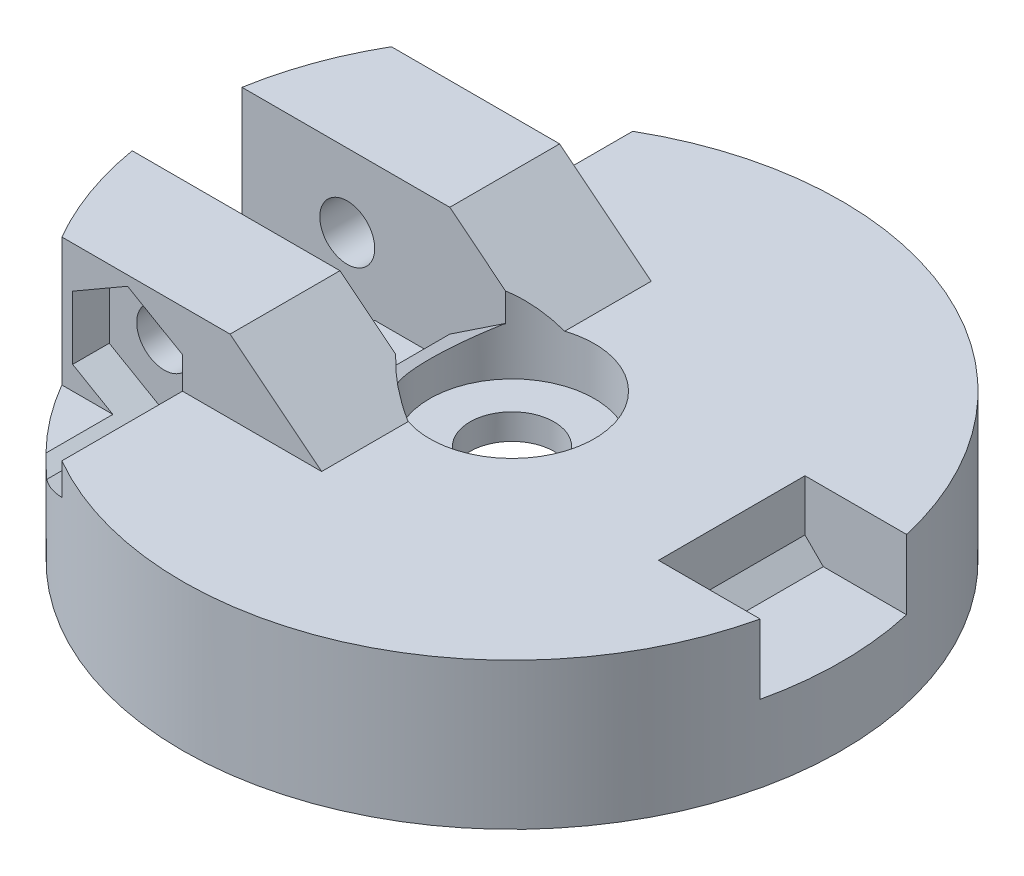
SolidWorks part; units mm, degrees
ref_plane "Front Plane" through (0, 0, 0) normal (0, 0, 1) x (1, 0, 0)
ref_plane "Top Plane" through (0, 0, 0) normal (0, 1, 0) x (1, 0, 0)
ref_plane "Right Plane" through (0, 0, 0) normal (1, 0, 0) x (0, 0, -1)
sketch "Sketch1" plane through (0, 0, 0) normal (0, 1, 0) x (1, 0, 0)
  circle A0 centre (0, 0) radius 9
  dimension "D1" = 18
extrude "Boss-Extrude1" add sketch "Sketch1" along normal blind 6
sketch "Sketch2" plane through (0, 6, 0) normal (0, 1, 0) x (1, 0, 0)
  circle A0 centre (0, 0) radius 1.15
  dimension "D1" = 2.3
extrude "Cut-Extrude1" cut sketch "Sketch2" against normal through all
sketch "Sketch5" plane through (0, 6, 0) normal (0, 1, 0) x (1, 0, 0)
  line L1 (-3.2, 4.5) -> (-7.7942, 4.5)
  line L2 (-3.2, 4.5) -> (-3.2, 8.4119)
  line L3 (-3.2, 8.4119) -> (-7.7942, 8.4119)
  line L4 (-7.7942, 4.5) -> (-7.7942, 8.4119)
  circle A2 centre (0, 0) radius 9 construction
  dimension "D1" = 3.2
  dimension "D2" = 4.5
extrude "Cut-Extrude3" cut sketch "Sketch5" against normal blind 3.5
mirror "Mirror1" about plane through (0, 0, 0) normal (0, 0, 1) of "Cut-Extrude3"
sketch "Sketch6" plane through (0, 6, 0) normal (0, 1, 0) x (1, 0, 0)
  line L0 (-3.2, -4.5) -> (-3.2, -8.4119) construction
  line L1 (-3.2, 9) -> (23.0525, 9)
  line L2 (-3.2, 9) -> (-3.2, -20.0526)
  line L3 (-3.2, -20.0526) -> (23.0525, -20.0526)
  line L4 (23.0525, 9) -> (23.0525, -20.0526)
  arc A0 (-3.2, -8.4119) -> (-3.2, 8.4119) centre (0, 0) ccw construction
extrude "Cut-Extrude4" cut sketch "Sketch6" against normal blind 2
sketch "Sketch7" plane through (0, 6, 0) normal (0, 1, 0) x (1, 0, 0)
  line L0 (-3.2, 4.5) -> (-3.2, -4.5) construction
  line L1 (-3.2, -1.5) -> (-12.173, -1.5)
  line L2 (-3.2, -1.5) -> (-3.2, 1.5)
  line L3 (-3.2, 1.5) -> (-12.173, 1.5)
  line L4 (-12.173, -1.5) -> (-12.173, 1.5)
  dimension "D1" = 1.5
  dimension "D2" = 3
extrude "Cut-Extrude5" cut sketch "Sketch7" against normal blind 3.7
sketch "Sketch11" plane through (0, 0, 0) normal (0, -1, 0) x (1, 0, 0)
  circle A0 centre (0, 0) radius 5.5
  dimension "D1" = 11
extrude "Cut-Extrude7" cut sketch "Sketch11" against normal blind 2
sketch "Sketch12" plane through (0, 4, 0) normal (0, 1, 0) x (1, 0, 0)
  line L1 (6, -2) -> (11.6408, -2)
  line L2 (6, -2) -> (6, 2)
  line L3 (6, 2) -> (11.6408, 2)
  line L4 (11.6408, -2) -> (11.6408, 2)
  arc A0 (-3.2, -8.4119) -> (-3.2, 8.4119) centre (0, 0) ccw construction
  dimension "D1" = 6
  dimension "D2" = 2
  dimension "D3" = 2
extrude "Cut-Extrude8" cut sketch "Sketch12" against normal blind 1.9
hole_wizard "CBORE for M1.4 Hex Socket Head Cap Screw1" positions "Sketch8" profile "Sketch9" counterbore size "M1.4" standard "DIN"
sketch "Sketch8" plane through (0, 0, -4.5) normal (0, 0, -1) x (-1, 0, 0)
  line L0 (7.7942, 6) -> (3.2, 6) construction
  point P0 (6, 4)
  dimension "D1" = 2
  dimension "D2" = 6
sketch "Sketch9" plane through (-6, 4, -4.5) normal (1, 0, 0) x (0, 1, 0)
  line L0 (0, 0) -> (0, 10.4506)
  line L1 (0, 10.4506) -> (0.75, 10)
  line L2 (0.75, 10) -> (0.75, 1)
  line L3 (0.75, 1) -> (1.35, 1)
  line L4 (1.35, 1) -> (1.35, 0)
  line L5 (1.35, 0) -> (0, 0)
  line L10 (0, 10.4506) -> (-0.75, 10) construction
  line L11 (0, -6.35) -> (0, 107.95) construction
  dimension "Hole Dia." = 1.5
  dimension "Hole Depth" = 10
  dimension "C'Bore Dia." = 2.7
  dimension "C'Bore Depth" = 1
  dimension "Drill Angle" = 118
fillet "Fillet7" radius 0.5 1 edges at (0, 2, -5.5) type face fillet first side face at (0, 2, -5.5) second side face at (0, 2, -5.5)
sketch "Sketch16" plane through (0, 0, 2) normal (0, 0, -1) x (-1, 0, 0)
  line L0 (-6, 2.1) -> (-6.5, 2.1)
  line L1 (-6, 2.1) -> (-8.775, 2.1) construction
  line L2 (-6.5, 2.1) -> (-6, 2.6)
  line L3 (-6, 2.1) -> (-6, 4) construction
  line L4 (-6, 2.6) -> (-6, 2.1)
  dimension "D1" = 0.5
  dimension "D2" = 0.5
extrude "Boss-Extrude4" add sketch "Sketch16" along normal up to surface (4 mm away) up to face at (7.3875, 3.05, -2)
sketch "Sketch17" plane through (0, 0, 4.5) normal (0, 0, 1) x (1, 0, 0)
  line L0 (-7.7942, 2.5) -> (-7.7942, 6) construction
  line L1 (-4.5, 4.866) -> (-6, 5.7321)
  line L2 (-6, 5.7321) -> (-7.5, 4.866)
  line L3 (-7.5, 4.866) -> (-7.5, 3.134)
  line L4 (-7.5, 3.134) -> (-6, 2.2679)
  line L5 (-6, 2.2679) -> (-4.5, 3.134)
  line L6 (-4.5, 3.134) -> (-4.5, 4.866)
  circle A1 centre (-6, 4) radius 1.5 construction
  dimension "D1" = 1.5
extrude "Cut-Extrude9" cut sketch "Sketch17" against normal blind 1
sketch "Sketch20" plane through (0, 0, 1.5) normal (0, 0, -1) x (-1, 0, 0)
  line L0 (3.2, 4) -> (1.7, 4)
  line L1 (1.7, 4) -> (3.2, 3)
  line L2 (3.2, 2.3) -> (3.2, 4) construction
  line L3 (3.2, 3) -> (3.2, 4)
  dimension "D1" = 1.5
  dimension "D2" = 1
extrude "Cut-Extrude11" cut sketch "Sketch20" along direction (0, 0, 1) on the side of the normal up to surface (3 mm away) up to face at (-6.75, 4, -1.5)
sketch "Sketch21" plane through (0, 0, -4.5) normal (0, 0, -1) x (-1, 0, 0)
  line L0 (3.2, 6) -> (3.2, 4)
  line L1 (3.2, 4) -> (0.7, 4)
  line L2 (0.7, 4) -> (3.2, 6)
  dimension "D1" = 2.5
extrude "Boss-Extrude5" add sketch "Sketch21" along direction (0, 0, 1) on the side against the normal up to surface (3 mm away) up to face at (-6.75, 4, -1.5)
sketch "Sketch22" plane through (0, 0, 4.5) normal (0, 0, 1) x (1, 0, 0)
  line L0 (-3.2, 6) -> (-3.2, 4)
  line L1 (-3.2, 4) -> (-0.7, 4)
  line L2 (-0.7, 4) -> (-3.2, 6)
  dimension "D1" = 2.5
extrude "Boss-Extrude6" add sketch "Sketch22" against normal up to surface (3 mm away) up to face at (-5.25, 4, 1.5)
sketch "Sketch10" plane through (0, 4, 0) normal (0, 1, 0) x (1, 0, 0)
  circle A0 centre (0, 0) radius 2.25
  dimension "D1" = 4.5
extrude "Cut-Extrude6" cut sketch "Sketch10" against normal blind 1.3 and the other way blind 3
sketch "Sketch24" plane through (0, 0, 4.5) normal (0, 0, 1) x (1, 0, 0)
  line L3 (-3.2, 2.5) -> (-3.2, 4)
  line L4 (-3.2, 2.5) -> (-5.5981, 2.5)
  line L5 (-5.5981, 2.5) -> (-4.5, 3.134)
  line L6 (-3.2, 4) -> (-4.5, 4)
  line L7 (-4.5, 3.134) -> (-4.5, 4.866) construction
  line L8 (-4.5, 4) -> (-4.5, 3.134)
extrude "Boss-Extrude8" add sketch "Sketch24" along normal up to surface (3.9119 mm away) up to face at (-2.6435, 3.675, 0)
mirror "Mirror4" about plane through (0, 0, 0) normal (0, 0, 1) of "Boss-Extrude8"
sketch "Sketch25" plane through (0, 0, 4.5) normal (0, 0, 1) x (1, 0, 0)
  line L0 (-5.5981, 2.5) -> (-6.4019, 2.5)
  line L1 (-6.4019, 2.5) -> (-6, 2.2679)
  line L2 (-6, 2.2679) -> (-5.5981, 2.5)
extrude "Cut-Extrude12" cut sketch "Sketch25" along normal blind 3
sketch "Sketch26" plane through (0, 2.3, 0) normal (0, 1, 0) x (1, 0, 0)
  line L1 (-6.95, 1.5) -> (-5.25, 1.5)
  line L2 (-6.95, 1.5) -> (-6.95, -1.5)
  line L3 (-6.95, -1.5) -> (-5.25, -1.5)
  line L4 (-5.25, 1.5) -> (-5.25, -1.5)
  dimension "D1" = 1.7
extrude "Cut-Extrude13" cut sketch "Sketch26" against normal blind 0.3
equation "\"D2@Sketch7\"=\"D1@Sketch7\"*2"
equation "\"D3@Sketch12\"=\"D2@Sketch12\""
equation "\"D2@Sketch16\"=.5"
equation "\"D2@Sketch20\"=1"
